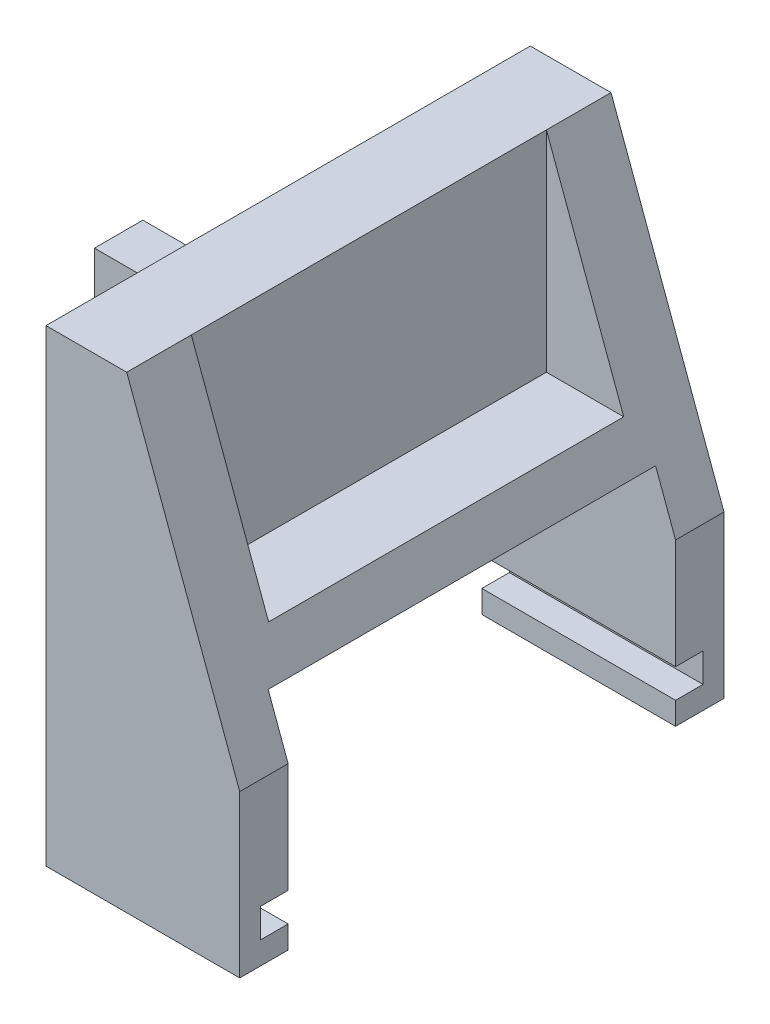
SolidWorks part; units mm, degrees
ref_plane "Front Plane" through (0, 0, 0) normal (0, 0, 1) x (1, 0, 0)
ref_plane "Top Plane" through (0, 0, 0) normal (0, 1, 0) x (1, 0, 0)
ref_plane "Right Plane" through (0, 0, 0) normal (1, 0, 0) x (0, 0, -1)
sketch "Sketch1" plane through (0, 0, 0) normal (0, 0, 1) x (1, 0, 0)
  line L0 (0, 0) -> (0, -29)
  line L1 (0, -29) -> (12, -29)
  line L2 (12, -29) -> (12, -19)
  line L3 (12, -19) -> (5, 0)
  line L4 (5, 0) -> (0, 0)
  dimension "D1" = 29
  dimension "D2" = 12
  dimension "D3" = 10
  dimension "D4" = 5
extrude "Boss-Extrude1" add sketch "Sketch1" against normal blind 30
sketch "Sketch4" plane through (0, 0, 0) normal (-1, 0, 0) x (0, 0, 1)
  line L0 (-30, 0) -> (-30, -29) construction
  line L1 (-27, -15.6386) -> (-3, -15.6386)
  line L2 (-27, -15.6386) -> (-27, -29.6386)
  line L3 (-27, -29.6386) -> (-3, -29.6386)
  line L4 (-3, -15.6386) -> (-3, -29.6386)
  point P4 (-27, -22.6386)
  dimension "D1" = 24
  dimension "D2" = 14
  dimension "D3" = 3
extrude "Cut-Extrude2" cut sketch "Sketch4" against normal blind 25 contours L2 L1 L4 L3
sketch "Sketch5" plane through (0, 0, 0) normal (-1, 0, 0) x (0, 0, 1)
  line L0 (-3, -15.6386) -> (-3, -29) construction
  line L1 (-3, -25.8) -> (-1.3, -25.8)
  line L2 (-3, -25.8) -> (-3, -27.6)
  line L3 (-3, -27.6) -> (-1.3, -27.6)
  line L4 (-1.3, -25.8) -> (-1.3, -27.6)
  line L5 (-3, -29) -> (0, -29) construction
  dimension "D1" = 1.8
  dimension "D2" = 1.7
  dimension "D3" = 1.4
extrude "Cut-Extrude3" cut sketch "Sketch5" against normal blind 15
ref_plane "Plane1" through (0, 0, -15) normal (0, 0, 1) x (1, 0, 0)
mirror "Mirror1" about plane through (0, 0, -15) normal (0, 0, 1) of "Cut-Extrude3"
sketch "Sketch6" plane through (0, 0, -15) normal (0, 0, 1) x (1, 0, 0)
  line L0 (5, 0) -> (5, -13)
  line L1 (5, -13) -> (9.7895, -13)
  line L2 (12, -19) -> (5, 0) construction
  line L3 (9.7895, -13) -> (5, 0)
  dimension "D1" = 13
extrude "Cut-Extrude4" cut sketch "Sketch6" against normal mid plane 22
ref_plane "Plane2" through (0, -15, 0) normal (0, 1, 0) x (1, 0, 0)
sketch "Sketch7" plane through (0, -15, 0) normal (0, 1, 0) x (1, 0, 0)
  line L0 (0, 15) -> (-5, 15)
  line L1 (0, 30) -> (0, 0) construction
  line L2 (-6.6, 15) -> (6.6, 15) construction
  line L3 (-5, 15) -> (-10.6569, 20.6569)
  line L4 (-10.6569, 20.6569) -> (-14.6569, 20.6569)
  line L5 (0, 12) -> (-6.2426, 12)
  line L6 (-6.2426, 12) -> (-11.8995, 17.6569)
  line L7 (-11.8995, 17.6569) -> (-14.6569, 17.6569)
  line L8 (-14.6569, 20.6569) -> (-14.6569, 17.6569)
  line L9 (0, 12) -> (0, 15)
  dimension "D1" = 3
extrude "Boss-Extrude2" add sketch "Sketch7" along normal blind 3
